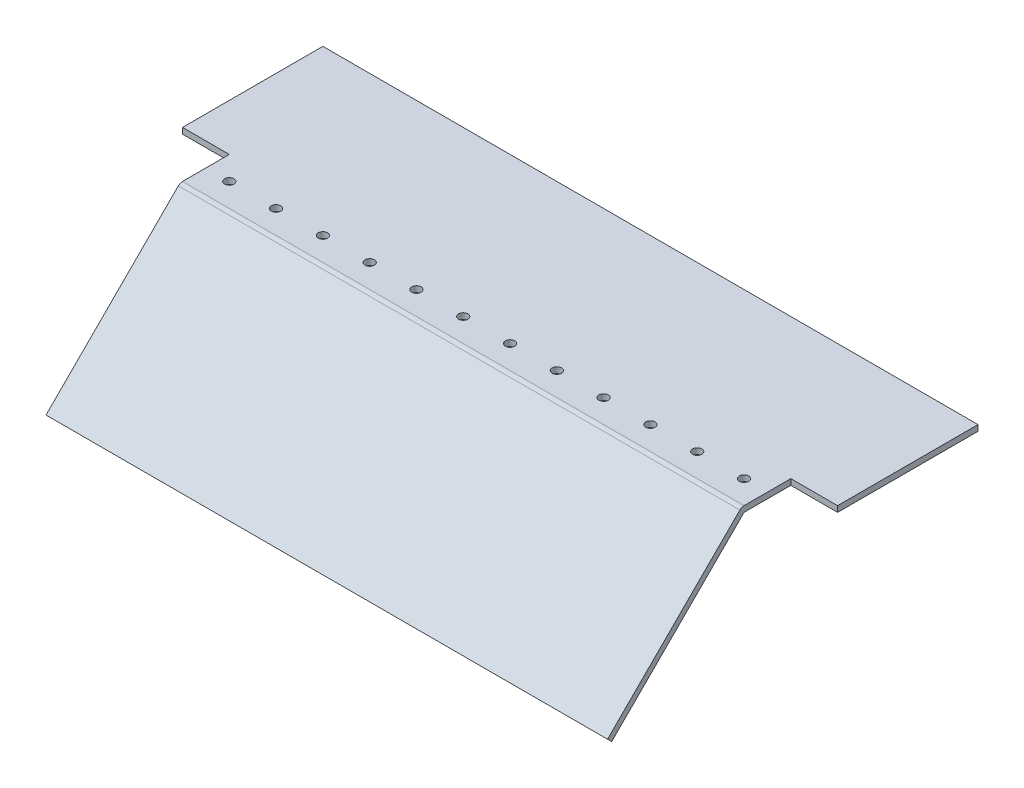
SolidWorks part; units mm, degrees
material "5052-H32"
ref_plane "Front Plane" through (0, 0, 0) normal (0, 0, 1) x (1, 0, 0)
ref_plane "Top Plane" through (0, 0, 0) normal (0, 1, 0) x (1, 0, 0)
ref_plane "Right Plane" through (0, 0, 0) normal (1, 0, 0) x (0, 0, -1)
sketch "Sketch1" plane through (0, 0, 0) normal (1, 0, 0) x (0, 0, -1)
  line L0 (-2.2451, 2.2451) -> (0, 0) construction
  line L2 (0, 0) -> (-71.842, -71.842)
  line L3 (-71.842, -71.842) -> (-74.0871, -69.597)
  line L4 (-2.2451, 2.2451) -> (-74.0871, -69.597)
  line L5 (0, 0) -> (101.6, 0)
  line L7 (0, 3.175) -> (101.6, 3.175)
  line L8 (101.6, 0) -> (101.6, 3.175)
  line L9 (0, 3.175) -> (0, 0)
  arc A1 (-2.2451, 2.2451) -> (0, 3.175) centre (0, 0) cw
  dimension "D3" = 101.6
  dimension "D1" = 101.6
  dimension "D2" = 3.175
  dimension "D5" = 135
extrude "Initial MidPlane Extrude" add sketch "Sketch1" along normal mid plane 304.8 contours L0 L4 L3 L2 | L7 L9 L5 L8 | A1 L0 L9 region at (0, 1.9057, 0.7894) region at (0, -34.7985, 37.0436) region at (0, 1.5875, -50.8)
extrude "ReExtrude For Wings." add sketch "Sketch1<3>" along normal mid plane 355.6 contours L7 L9 L5 L8 region at (0, 1.5875, -50.8)
sketch "Sketch1<3>" plane through (0, 0, 0) normal (1, 0, 0) x (0, 0, -1) same geometry as "Sketch1"
sketch "Sketch2" plane through (0, 3.175, 0) normal (0, 1, 0) x (1, 0, 0)
  line L1 (-152.4, 0) -> (-177.8, 0)
  line L2 (-152.4, 0) -> (-152.4, 25.4)
  line L3 (-152.4, 25.4) -> (-177.8, 25.4)
  line L4 (-177.8, 0) -> (-177.8, 25.4)
  line L5 (-177.8, 0) -> (-177.8, 101.6) construction
  line L6 (177.8, 0) -> (177.8, 101.6) construction
  line L7 (152.4, 0) -> (177.8, 0)
  line L8 (152.4, 0) -> (152.4, 25.4)
  line L9 (152.4, 25.4) -> (177.8, 25.4)
  line L10 (177.8, 0) -> (177.8, 25.4)
  dimension "D1" = 25.4
extrude "Bandsaw Cut" cut sketch "Sketch2" against normal through all
sketch "Sketch3" plane through (0, 3.175, 0) normal (0, 1, 0) x (1, 0, 0)
  line L0 (-152.4, 12.7) -> (-139.7, 12.7) construction
  line L1 (-152.4, 0) -> (-152.4, 25.4) construction
  circle A0 centre (-139.7, 12.7) radius 2.54
  dimension "D1" = 12.7
  dimension "D2" = 5.08
extrude "Initial Mounting Hole" cut sketch "Sketch3" against normal through all
pattern_linear "Mounting Hole Pattern" count 12 spacing 25.4 along (1, 0, 0) of "Initial Mounting Hole"
